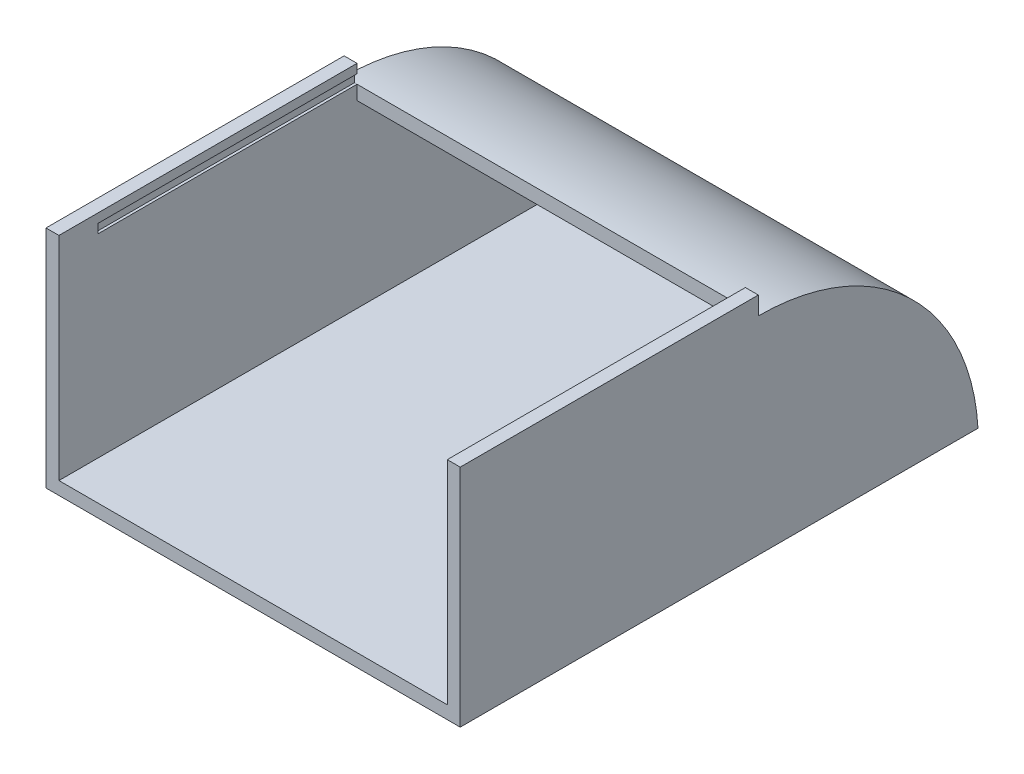
SolidWorks part; units mm, degrees
ref_plane "Front Plane" through (0, 0, 0) normal (0, 0, 1) x (1, 0, 0)
ref_plane "Top Plane" through (0, 0, 0) normal (0, 1, 0) x (1, 0, 0)
ref_plane "Right Plane" through (0, 0, 0) normal (1, 0, 0) x (0, 0, -1)
sketch "Sketch1" plane through (0, 0, 0) normal (1, 0, 0) x (0, 0, -1)
  line L1 (100, -40) -> (-100, -40)
  line L2 (100, -40) -> (100, 40)
  line L3 (100, 40) -> (-100, 40)
  line L4 (-100, -40) -> (-100, 40)
  line L5 (100, -40) -> (-100, 40) construction
  line L6 (100, 40) -> (-100, -40) construction
  point P0 (0, 0)
  dimension "D1" = 80
  dimension "D2" = 200
extrude "Boss-Extrude1" add sketch "Sketch1" along normal mid plane 160
sketch "Sketch2" plane through (0, 0, 100) normal (0, 0, 1) x (1, 0, 0)
  line L1 (75, -35) -> (-75, -35)
  line L2 (75, -35) -> (75, 35)
  line L3 (75, 35) -> (-75, 35)
  line L4 (-75, -35) -> (-75, 35)
  line L5 (75, -35) -> (-75, 35) construction
  line L6 (75, 35) -> (-75, -35) construction
  point P0 (0, 0)
  dimension "D1" = 150
  dimension "D2" = 70
extrude "Cut-Extrude2" cut sketch "Sketch2" against normal blind 190
fillet "Fillet5" radius 85 2 edges at (0, 35, -90) (0, 40, -100)
sketch "Sketch8" plane through (0, 40, 0) normal (0, 1, 0) x (1, 0, 0)
  line L0 (0, 15.1472) -> (-75, 15.1472)
  line L1 (80, 15.1472) -> (-80, 15.1472) construction
  line L2 (0, 15.1472) -> (75, 15.1472)
  line L3 (-75, 15.1472) -> (-75, -100)
  line L4 (75, 15.1472) -> (75, -100)
  line L5 (80, -100) -> (-80, -100) construction
  line L6 (75, -100) -> (-75, -100)
  dimension "D1" = 75
  dimension "D2" = 75
extrude "Cut-Extrude6" cut sketch "Sketch8" against normal blind 10
sketch "Sketch9" plane through (0, 40, 0) normal (0, 1, 0) x (1, 0, 0)
  line L1 (-80, 15.1472) -> (-75, 15.1472)
  line L2 (-80, 15.1472) -> (-80, -100)
  line L3 (-80, -100) -> (-75, -100)
  line L4 (-75, 15.1472) -> (-75, -100)
extrude "Boss-Extrude2" add sketch "Sketch9" along normal blind 7
sketch "Sketch10" plane through (0, 40, 0) normal (0, 1, 0) x (1, 0, 0)
  line L1 (75, 15.1472) -> (80, 15.1472)
  line L2 (75, 15.1472) -> (75, -100)
  line L3 (75, -100) -> (80, -100)
  line L4 (80, 15.1472) -> (80, -100)
extrude "Boss-Extrude3" add sketch "Sketch10" along normal blind 7
sketch "Sketch13" plane through (-75, 0, 0) normal (1, 0, 0) x (0, 0, -1)
  line L1 (15.1472, 40) -> (-84.8528, 40)
  line L2 (15.1472, 40) -> (15.1472, 43.5)
  line L3 (15.1472, 43.5) -> (-84.8528, 43.5)
  line L4 (-84.8528, 40) -> (-84.8528, 43.5)
  dimension "D1" = 100
  dimension "D2" = 3.5
extrude "Cut-Extrude9" cut sketch "Sketch13" against normal blind 1
sketch "Sketch14" plane through (75, 0, 0) normal (-1, 0, 0) x (0, 0, 1)
  line L1 (-15.1472, 40) -> (84.8528, 40)
  line L2 (-15.1472, 40) -> (-15.1472, 43.5)
  line L3 (-15.1472, 43.5) -> (84.8528, 43.5)
  line L4 (84.8528, 40) -> (84.8528, 43.5)
  dimension "D1" = 3.5
  dimension "D2" = 100
extrude "Cut-Extrude10" cut sketch "Sketch14" against normal blind 1
